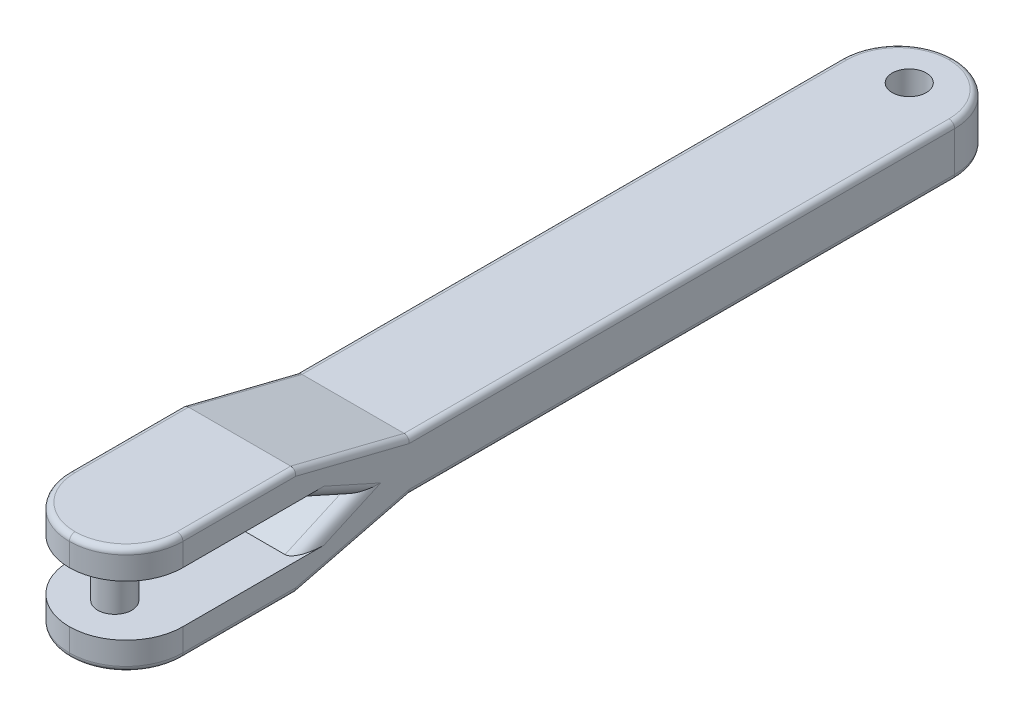
SolidWorks part; units mm, degrees
ref_plane "Front Plane" through (0, 0, 0) normal (0, 0, 1) x (1, 0, 0)
ref_plane "Top Plane" through (0, 0, 0) normal (0, 1, 0) x (1, 0, 0)
ref_plane "Right Plane" through (0, 0, 0) normal (1, 0, 0) x (0, 0, -1)
sketch "Sketch2" plane through (0, 0, 0) normal (1, 0, 0) x (0, 0, -1)
  line L0 (0, 22.5) -> (0, -22.5) construction
  line L1 (0, -22.5) -> (40, -22.5)
  line L2 (40, -22.5) -> (40, 22.5)
  line L3 (40, 22.5) -> (0, 22.5)
  line L4 (0, 22.5) -> (-490, 22.5)
  line L5 (0, -22.5) -> (-490, -22.5)
  line L6 (-490, -22.5) -> (-590, -47.5)
  line L7 (-590, -47.5) -> (-740, -47.5)
  line L8 (-740, -47.5) -> (-740, -22.5)
  line L9 (-740, -22.5) -> (-590, -22.5)
  line L10 (-590, -22.5) -> (-540, 0)
  line L11 (-540, 0) -> (-590, 22.5)
  line L12 (-590, 22.5) -> (-740, 22.5)
  line L13 (-740, 22.5) -> (-740, 47.5)
  line L14 (-740, 47.5) -> (-590, 47.5)
  line L15 (-590, 47.5) -> (-490, 22.5)
  line L16 (-490, -22.5) -> (-490, 22.5) construction
  line L17 (-490, 0) -> (-540, 0) construction
  line L18 (-740, -22.5) -> (-740, 22.5) construction
  line L19 (-540, 0) -> (-740, 0) construction
  line L20 (-590, 22.5) -> (-590, -22.5) construction
  line L21 (-590, 47.5) -> (-590, 22.5) construction
  line L22 (-590, -22.5) -> (-590, -47.5) construction
  line L23 (-700, -22.5) -> (-700, 22.5) construction
  point P4 (0, 0)
  dimension "D1" = 45
  dimension "D2" = 25
  dimension "D3" = 50
  dimension "D4" = 150
  dimension "D5" = 40
  dimension "D6" = 700
  dimension "D7" = 100
  dimension "D8" = 40
extrude "Boss-Extrude1" add sketch "Sketch2" along normal mid plane 100
sketch "Sketch3" plane through (0, -22.5, 0) normal (0, -1, 0) x (1, 0, 0)
  circle A0 centre (0, 0) radius 15
  dimension "D1" = 30
extrude "Cut-Extrude1" cut sketch "Sketch3" against normal through all both and the other way through all
sketch "Sketch4" plane through (0, -47.5, 0) normal (0, -1, 0) x (1, 0, 0)
  line L0 (0, 740) -> (0, 700) construction
  line L1 (50, 740) -> (-50, 740) construction
  circle A0 centre (0, 700) radius 15
  dimension "D1" = 30
  dimension "D2" = 40
extrude "Boss-Extrude2" add sketch "Sketch4" against normal up to surface (95 mm away) up to face at (0, 47.5, 665)
fillet "Fillet1" radius 50 2 edges at (50, 0, -40) (-50, 0, -40)
fillet "Fillet2" radius 10 4 edges at (50, -11.25, 565) (50, 11.25, 565) (-50, -11.25, 565) (-50, 11.25, 565)
fillet "Fillet3" radius 50 4 edges at (-50, -35, 740) (-50, 35, 740) (50, 35, 740) (50, -35, 740)
fillet "Fillet4" radius 5 20 edges at (50, 47.5, 640) (35.3553, 47.5, 725.3553) (-35.3553, 47.5, 725.3553) (50, -47.5, 640) (35.3553, -47.5, 725.3553) (-35.3553, -47.5, 725.3553) (50, 22.5, 250) (35.3553, 22.5, -25.3553) (-35.3553, 22.5, -25.3553) (50, -22.5, 250) (35.3553, -22.5, -25.3553) (-35.3553, -22.5, -25.3553) (50, 35, 540) (-50, 47.5, 640) (-50, 35, 540) (50, -35, 540) (-50, -47.5, 640) (-50, -35, 540) (-50, 22.5, 250) (-50, -22.5, 250)
